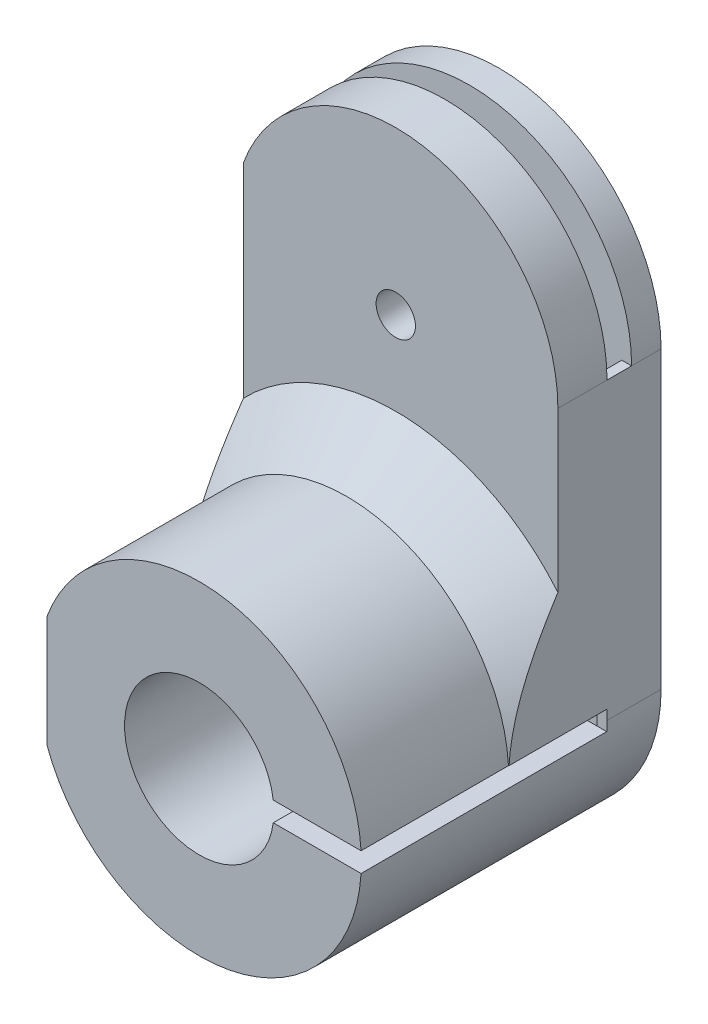
SolidWorks part; units mm, degrees
ref_plane "Front Plane" through (0, 0, 0) normal (0, 0, 1) x (1, 0, 0)
ref_plane "Top Plane" through (0, 0, 0) normal (0, 1, 0) x (1, 0, 0)
ref_plane "Right Plane" through (0, 0, 0) normal (1, 0, 0) x (0, 0, -1)
sketch "Sketch1" plane through (0, 0, 0) normal (0, 0, 1) x (1, 0, 0)
  line L0 (-16.5, 0) -> (-16.5, 30)
  line L1 (16.5, 30) -> (16.5, 0)
  arc A0 (-16.5, 0) -> (16.5, 0) centre (0, 0) ccw
  circle A1 centre (0, 30) radius 2
  circle A2 centre (0, 0) radius 7.6
  arc A3 (-16.5, 30) -> (16.5, 30) centre (0, 30) cw
  dimension "D1" = 33
  dimension "D2" = 15.2
  dimension "D4" = 4
  dimension "D3" = 30
extrude "Boss-Extrude1" add sketch "Sketch1" along normal blind 5
sketch "Sketch2" plane through (0, 0, 5) normal (0, 0, 1) x (1, 0, 0)
  circle A0 centre (0, 0) radius 7.6
  circle A1 centre (0, 0) radius 16.5
  arc A2 (-16.5, 0) -> (16.5, 0) centre (0, 0) ccw construction
  circle A3 centre (0, 0) radius 7.6 construction
extrude "Boss-Extrude2" add sketch "Sketch2" along normal blind 20
chamfer "Chamfer1" distance 5 angle 45 1 edges at (0, 16.5, 5)
ref_plane "Plane1" through (0, 0, -2.5) normal (0, 0, -1) x (-1, 0, 0)
sketch "Sketch3" plane through (0, 0, -2.5) normal (0, 0, -1) x (-1, 0, 0)
  line L2 (16.5, 0) -> (16.5, 30)
  line L3 (16.5, 0) -> (16.5, 30)
  line L4 (-16.5, 30) -> (-16.5, 0)
  line L5 (-16.5, 30) -> (-16.5, 0)
  circle A0 centre (0, 0) radius 7.6
  circle A1 centre (0, 30) radius 2
  arc A2 (-16.5, 0) -> (16.5, 0) centre (0, 0) ccw
  arc A3 (-16.5, 0) -> (16.5, 0) centre (0, 0) ccw
  arc A4 (16.5, 30) -> (-16.5, 30) centre (0, 30) ccw
  arc A5 (16.5, 30) -> (-16.5, 30) centre (0, 30) ccw
  circle A6 centre (0, 30) radius 2 construction
  circle A7 centre (0, 0) radius 7.6 construction
  dimension "D1" = 0
extrude "Boss-Extrude3" add sketch "Sketch3" along normal blind 3 separate body
sketch "Sketch6" plane through (0, 0, 25) normal (0, 0, 1) x (1, 0, 0)
  line L0 (0, 0) -> (24.6132, 0)
sketch "Sketch7" plane through (0, 0, -5.5) normal (0, 0, -1) x (-1, 0, 0)
  line L0 (-16.5, 30) -> (-16.5, 0)
  line L1 (-15.5, 30) -> (-15.5, 0)
  line L2 (-16.5, 30) -> (-15.5, 30)
  line L3 (16.5, 0) -> (15.5, 0)
  arc A0 (-16.5, 0) -> (16.5, 0) centre (0, 0) ccw
  arc A1 (-15.5, 0) -> (15.5, 0) centre (0, 0) ccw
  dimension "D1" = 1
extrude "Boss-Extrude5" add sketch "Sketch7" against normal blind 6
extrude "Cut-Extrude-Thin3" cut sketch "Sketch6" against normal up to surface and the other way through all thin up to face at (-0.1667, 15.1667, 0) thin type two direction wall 1 second wall 1
sketch "Sketch8" plane through (-16.5, 0, 0) normal (-1, 0, 0) x (0, 0, 1)
  line L1 (30.5308, -32.3754) -> (-8.5862, -32.3754)
  line L2 (30.5308, -32.3754) -> (30.5308, 56.1299)
  line L3 (30.5308, 56.1299) -> (-8.5862, 56.1299)
  line L4 (-8.5862, -32.3754) -> (-8.5862, 56.1299)
extrude "Cut-Extrude1" cut sketch "Sketch8" against normal blind 1
